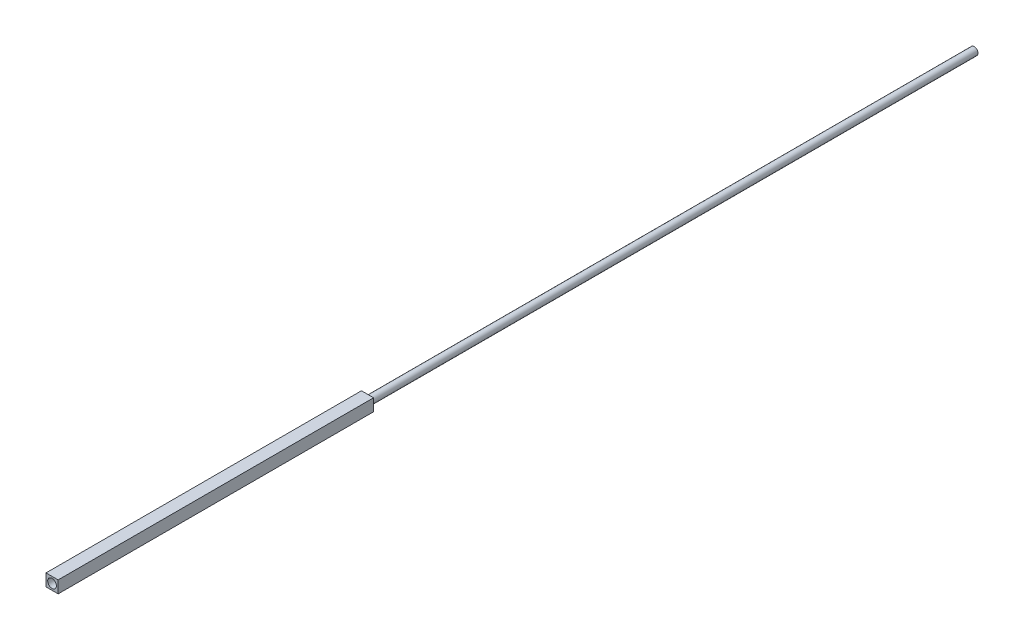
SolidWorks part; units mm, degrees
material "Hexcel AS4C (3000 Filaments)"
ref_plane "Front Plane" through (0, 0, 0) normal (0, 0, 1) x (1, 0, 0)
ref_plane "Top Plane" through (0, 0, 0) normal (0, 1, 0) x (1, 0, 0)
ref_plane "Right Plane" through (0, 0, 0) normal (1, 0, 0) x (0, 0, -1)
sketch "Sketch1" plane through (0, 0, 0) normal (0, 0, 1) x (1, 0, 0)
  circle A0 centre (0, 0) radius 1.9939
  circle A1 centre (0, 0) radius 1.6939
  dimension "D1" = 3.9878
  dimension "D2" = 0.3
extrude "Boss-Extrude1" add sketch "Sketch1" along normal blind 330.2
sketch "Sketch2" plane through (0, 0, 0) normal (1, 0, 0) x (0, 0, -1)
  line L0 (0, -1.9939) -> (0, 1.9939) construction
  line L1 (0, 1.016) -> (-2.54, 1.016)
  line L2 (0, 1.016) -> (0, -1.016)
  line L3 (0, -1.016) -> (-2.54, -1.016)
  line L4 (-2.54, 1.016) -> (-2.54, -1.016)
  point P9 (0, 0)
  dimension "D1" = 2.032
  dimension "D2" = 2.54
extrude "Cut-Extrude1" cut sketch "Sketch2" against normal up to surface (1.7156 mm away) up to face at (1.9939, 0, 330.2)
ref_axis "Axis1" through (0, 0, 330.2) along (0, 0, -1)
sketch "Sketch5" plane through (0, 0, 330.2) normal (0, 0, 1) x (1, 0, 0)
  line L1 (-3.175, 3.175) -> (3.175, 3.175)
  line L2 (-3.175, 3.175) -> (-3.175, -3.175)
  line L3 (-3.175, -3.175) -> (3.175, -3.175)
  line L4 (3.175, 3.175) -> (3.175, -3.175)
  line L5 (-3.175, 3.175) -> (3.175, -3.175) construction
  line L6 (-3.175, -3.175) -> (3.175, 3.175) construction
  circle A0 centre (0, 0) radius 2.286
  point P0 (0, 0)
  dimension "D3" = 4.572
  dimension "D1" = 6.35
  dimension "D2" = 6.35
extrude "Boss-Extrude3" add sketch "Sketch5" along normal blind 152.4 and the other way blind 12.7 separate body
